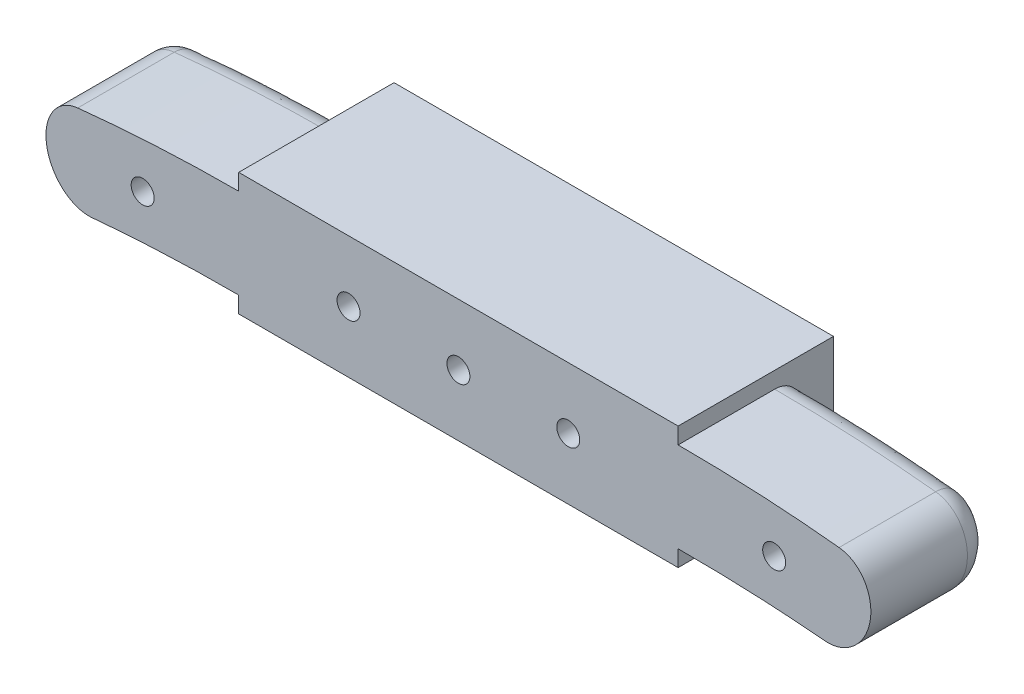
SolidWorks part; units mm, degrees
note: The reader was unsure of these and kept them because the rebuilt part matched: shared geometry of "Sketch1<4>".
material "ABS"
ref_plane "Front Plane" through (0, 0, 0) normal (0, 0, 1) x (1, 0, 0)
ref_plane "Top Plane" through (0, 0, 0) normal (0, 1, 0) x (1, 0, 0)
ref_plane "Right Plane" through (0, 0, 0) normal (1, 0, 0) x (0, 0, -1)
sketch "Sketch1" plane through (0, 0, 0) normal (0, 0, 1) x (1, 0, 0)
  line L0 (0, 12) -> (0, -12) construction
  line L1 (-137.5, -120) -> (137.5, -120) construction
  line L2 (-137.5, -120) -> (-137.5, 120) construction
  line L3 (-137.5, 120) -> (137.5, 120) construction
  line L4 (137.5, -120) -> (137.5, 120) construction
  line L5 (-137.5, -120) -> (137.5, 120) construction
  line L6 (-137.5, 120) -> (137.5, -120) construction
  line L7 (-43, 0) -> (0, 0) construction
  line L8 (-43, 0) -> (-43, -378.76) construction
  line L9 (0, 12) -> (-43, 12)
  line L10 (0, -12) -> (-43, -12)
  line L11 (-43, 12) -> (-43, 8.8)
  line L12 (-43, -12) -> (-43, -8.8)
  line L13 (-43, -387.56) -> (-43, -378.76) construction
  line L16 (-43, -189.38) -> (-74.5, 7.1619) construction
  line L17 (-43, -189.38) -> (-82.2839, 6.2463) construction
  line L18 (0, 12) -> (0, -12)
  line L19 (-43, 8.8) -> (-43, -8.8)
  ellipse E0 centre (-43, -189.38) end of major axis (-268.5, -189.38) minor radius 189.38 construction
  ellipse E1 centre (-43, -189.38) end of major axis (202.5, -189.38) minor radius 198.18 construction
  ellipse E2 centre (-43, -189.38) end of major axis (202.5, -189.38) minor radius 180.58 construction
  ellipse E3 centre (-73.0639, -1.4345) end of major axis (-70.1463, -9.6976) minor radius 7.5002 (-74.5, 7.1619) -> (-71.7427, -10.0419) ccw
  ellipse E4 centre (-43, -189.38) end of major axis (202.5, -189.38) minor radius 198.18 (-43, 8.8) -> (-74.5, 7.1619) ccw
  ellipse E5 centre (-43, -189.38) end of major axis (192.7176, -191.4751) minor radius 180.5771 (-43, -8.8) -> (-71.7427, -10.0419) ccw
  point P0 (0, 0)
  point P32 (-269.6246, -189.38)
  point P33 (0, 0)
  point P34 (-268.5, -189.38)
  point P37 (-80.5, -2.637)
  point P38 (-278.1227, -189.38)
  point P48 (-275.8206, -189.38)
  point P54 (0, 0)
  point P55 (0, 0)
  point P56 (0, 0)
  point P57 (-71.7127, -10.1386)
  point P58 (-71.7427, -10.0419)
  dimension "D1" = 275
  dimension "D2" = 240
  dimension "D3" = 24
  dimension "D4" = 378.76
  dimension "D5" = 451
  dimension "D6" = 43
  dimension "D7" = 17.6
  dimension "D8" = 74.5
  dimension "D9" = 80.5
  dimension "D10" = 491
extrude "Boss-Extrude1" add sketch "Sketch1" against normal blind 6.5 contours L11 L19 L12 L10 L18 L9
extrude "Boss-Extrude2" add sketch "Sketch1<4>" along normal blind 23.9 contours E5 L19 E4 E3 | L11 L19 L12 L10 L18 L9
sketch "Sketch1<4>" plane through (0, 0, 0) normal (0, 0, 1) x (1, 0, 0) same geometry as "Sketch1"
fillet "Fillet1" radius 5 3 edges at (-57.3982, -9.0843, 0) (-80.5891, -2.1537, 0) (-58.7826, 8.39, 0)
sketch "Sketch2" plane through (0, 0, 23.9) normal (0, 0, 1) x (1, 0, 0)
  line L0 (-43, 0) -> (0, 0) construction
  line L1 (-80.5, -2.637) -> (-61.7964, -0.659) construction
  line L2 (-43, 0) -> (-61.7964, -0.659) construction
  line L3 (-21.5, 0) -> (0, 0) construction
  line L4 (-137.5, 120) -> (137.5, -120) construction
  line L5 (-43, 0) -> (-21.5, 0) construction
  circle A0 centre (-21.5, 0) radius 2.25
  circle A1 centre (-61.7964, -0.659) radius 2.25
  ellipse E0 centre (-43, -189.38) end of major axis (-268.5, -189.38) minor radius 189.38 construction
  dimension "D1" = 4.5
extrude "Cut-Extrude1" cut sketch "Sketch2" against normal through all both and the other way through all
mirror "Mirror1" about plane through (0, 0, -6.5) normal (-1, 0, 0) of bodies 103
sketch "Sketch3" plane through (0, 0, 23.9) normal (0, 0, 1) x (1, 0, 0)
  circle A0 centre (0, 0) radius 2.25
  dimension "D1" = 4.5
extrude "Cut-Extrude2" cut sketch "Sketch3" against normal through all both and the other way through all
